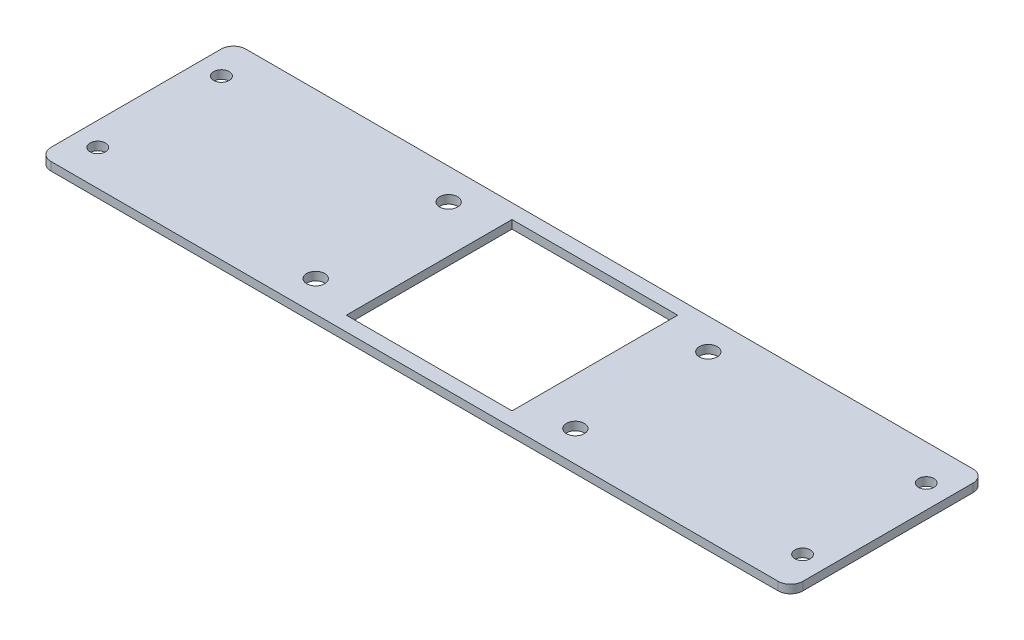
SolidWorks part; units mm, degrees
material "Acrylic (Medium-high impact)"
ref_plane "Front Plane" through (0, 0, 0) normal (0, 0, 1) x (1, 0, 0)
ref_plane "Top Plane" through (0, 0, 0) normal (0, 1, 0) x (1, 0, 0)
ref_plane "Right Plane" through (0, 0, 0) normal (1, 0, 0) x (0, 0, -1)
sketch "Sketch1" plane through (0, 0, 0) normal (0, 1, 0) x (1, 0, 0)
  line L0 (-60.8, -12.3481) -> (-60.8, -7.25) construction
  line L1 (-59.8, -6.25) -> (-53, -6.25) construction
  line L2 (-52, -7.25) -> (-52, -13.349) construction
  line L3 (-53, -14.35) -> (-58.8, -14.35) construction
  line L4 (-53, 6.25) -> (-59.8, 6.25) construction
  line L5 (-60.8, 7.25) -> (-60.8, 12.3481) construction
  line L6 (-58.8, 14.35) -> (-53, 14.35) construction
  line L7 (-52, 13.349) -> (-52, 7.25) construction
  line L8 (53, -6.25) -> (59.8, -6.25) construction
  line L9 (60.8, -7.25) -> (60.8, -12.3481) construction
  line L10 (58.8, -14.35) -> (53, -14.35) construction
  line L11 (52, -13.349) -> (52, -7.25) construction
  line L12 (60.8, 12.3481) -> (60.8, 7.25) construction
  line L13 (59.8, 6.25) -> (53, 6.25) construction
  line L14 (52, 7.25) -> (52, 13.349) construction
  line L15 (53, 14.35) -> (58.8, 14.35) construction
  line L16 (-60.8, -12.3481) -> (-60.8, -7.25)
  line L17 (-59.8, -6.25) -> (-53, -6.25)
  line L18 (-52, -7.25) -> (-52, -13.349)
  line L19 (-53, -14.35) -> (-58.8, -14.35)
  line L20 (-53, 6.25) -> (-59.8, 6.25)
  line L21 (-60.8, 7.25) -> (-60.8, 12.3481)
  line L22 (-58.8, 14.35) -> (-53, 14.35)
  line L23 (-52, 13.349) -> (-52, 7.25)
  line L24 (53, -6.25) -> (59.8, -6.25)
  line L25 (60.8, -7.25) -> (60.8, -12.3481)
  line L26 (58.8, -14.35) -> (53, -14.35)
  line L27 (52, -13.349) -> (52, -7.25)
  line L28 (60.8, 12.3481) -> (60.8, 7.25)
  line L29 (59.8, 6.25) -> (53, 6.25)
  line L30 (52, 7.25) -> (52, 13.349)
  line L31 (53, 14.35) -> (58.8, 14.35)
  line L32 (-60.8, 15.75) -> (60.8, 15.75)
  line L33 (104.5, 15.75) -> (-104.5, 15.75) construction
  line L34 (-60.8, -15.75) -> (60.8, -15.75)
  line L35 (-66.88, -15.75) -> (66.88, -15.75) construction
  arc A0 (-59.8, -6.25) -> (-60.8, -7.25) centre (-59.8, -7.25) ccw construction
  circle A1 centre (-57, 10) radius 1.6
  circle A2 centre (-57, 10) radius 1.6
  circle A3 centre (-57, -10) radius 1.6
  circle A4 centre (-57, -10) radius 1.6
  circle A5 centre (57, -10) radius 1.6
  circle A6 centre (57, -10) radius 1.6
  circle A7 centre (57, 10) radius 1.6
  circle A8 centre (57, 10) radius 1.6
  arc A9 (-52, -7.25) -> (-53, -6.25) centre (-53, -7.25) ccw construction
  arc A10 (-60.8, 7.25) -> (-59.8, 6.25) centre (-59.8, 7.25) ccw construction
  arc A11 (-53, 6.25) -> (-52, 7.25) centre (-53, 7.25) ccw construction
  arc A12 (60.8, -7.25) -> (59.8, -6.25) centre (59.8, -7.25) ccw construction
  arc A13 (53, -6.25) -> (52, -7.25) centre (53, -7.25) ccw construction
  arc A14 (59.8, 6.25) -> (60.8, 7.25) centre (59.8, 7.25) ccw construction
  arc A15 (52, 7.25) -> (53, 6.25) centre (53, 7.25) ccw construction
  arc A16 (-59.8, -6.25) -> (-60.8, -7.25) centre (-59.8, -7.25) ccw
  arc A17 (-52, -7.25) -> (-53, -6.25) centre (-53, -7.25) ccw
  arc A18 (-60.8, 7.25) -> (-59.8, 6.25) centre (-59.8, 7.25) ccw
  arc A19 (-53, 6.25) -> (-52, 7.25) centre (-53, 7.25) ccw
  arc A20 (60.8, -7.25) -> (59.8, -6.25) centre (59.8, -7.25) ccw
  arc A21 (53, -6.25) -> (52, -7.25) centre (53, -7.25) ccw
  arc A22 (59.8, 6.25) -> (60.8, 7.25) centre (59.8, 7.25) ccw
  arc A23 (52, 7.25) -> (53, 6.25) centre (53, 7.25) ccw
  ellipse E0 centre (-53, -13.349) end of major axis (-53, -14.35) minor radius 1 (-53, -14.35) -> (-52, -13.349) ccw construction
  ellipse E1 centre (-58.8, -12.3481) end of major axis (-58.8, -10.3461) minor radius 2 (-60.8, -12.3481) -> (-58.8, -14.35) ccw construction
  ellipse E2 centre (-58.8, 12.3481) end of major axis (-58.8, 14.35) minor radius 2 (-58.8, 14.35) -> (-60.8, 12.3481) ccw construction
  ellipse E3 centre (-53, 13.349) end of major axis (-53, 14.35) minor radius 1 (-52, 13.349) -> (-53, 14.35) ccw construction
  ellipse E4 centre (58.8, -12.3481) end of major axis (58.8, -14.35) minor radius 2 (58.8, -14.35) -> (60.8, -12.3481) ccw construction
  ellipse E5 centre (53, -13.349) end of major axis (53, -14.35) minor radius 1 (52, -13.349) -> (53, -14.35) ccw construction
  ellipse E6 centre (53, 13.349) end of major axis (53, 14.35) minor radius 1 (53, 14.35) -> (52, 13.349) ccw construction
  ellipse E7 centre (58.8, 12.3481) end of major axis (58.8, 10.3461) minor radius 2 (60.8, 12.3481) -> (58.8, 14.35) ccw construction
  ellipse E8 centre (-53, -13.349) end of major axis (-53, -14.35) minor radius 1 (-53, -14.35) -> (-52, -13.349) ccw
  ellipse E9 centre (-58.8, -12.3481) end of major axis (-58.8, -10.3461) minor radius 2 (-60.8, -12.3481) -> (-58.8, -14.35) ccw
  ellipse E10 centre (-58.8, 12.3481) end of major axis (-58.8, 14.35) minor radius 2 (-58.8, 14.35) -> (-60.8, 12.3481) ccw
  ellipse E11 centre (-53, 13.349) end of major axis (-53, 14.35) minor radius 1 (-52, 13.349) -> (-53, 14.35) ccw
  ellipse E12 centre (58.8, -12.3481) end of major axis (58.8, -14.35) minor radius 2 (58.8, -14.35) -> (60.8, -12.3481) ccw
  ellipse E13 centre (53, -13.349) end of major axis (53, -14.35) minor radius 1 (52, -13.349) -> (53, -14.35) ccw
  ellipse E14 centre (53, 13.349) end of major axis (53, 14.35) minor radius 1 (53, 14.35) -> (52, 13.349) ccw
  ellipse E15 centre (58.8, 12.3481) end of major axis (58.8, 10.3461) minor radius 2 (60.8, 12.3481) -> (58.8, 14.35) ccw
  dimension "D1" = 0
  dimension "D2" = 0
  dimension "D3" = 0
  dimension "D4" = 0
sketch "Sketch2" plane through (0, 0, 0) normal (0, 1, 0) x (1, 0, 0)
  line L1 (-60.8, -15.75) -> (60.8, -15.75)
  line L2 (-60.8, -15.75) -> (-60.8, 15.75)
  line L3 (-60.8, 15.75) -> (60.8, 15.75)
  line L4 (60.8, -15.75) -> (60.8, 15.75)
  circle A0 centre (-57, 10) radius 1.25
  circle A1 centre (-57, -10) radius 1.25
  circle A2 centre (57, 10) radius 1.25
  circle A3 centre (57, -10) radius 1.25
  dimension "D1" = 2.5
extrude "Boss-Extrude1" add sketch "Sketch2" against normal blind 1.35
fillet "Fillet1" radius 2 4 edges at (-60.8, -0.675, -15.75) (60.8, -0.675, -15.75) (60.8, -0.675, 15.75) (-60.8, -0.675, 15.75)
sketch "Sketch3" plane through (0, 0, 0) normal (0, 1, 0) x (1, 0, 0)
  line L4 (13.4, -13.4) -> (13.4, 13.4)
  line L5 (13.4, 13.4) -> (-13.4, 13.4)
  line L6 (-13.4, 13.4) -> (-13.4, -13.4)
  line L7 (-13.4, -13.4) -> (13.4, -13.4)
  line L8 (13.4, -13.4) -> (13.4, 13.4)
  line L9 (13.4, 13.4) -> (-13.4, 13.4)
  line L10 (-13.4, 13.4) -> (-13.4, -13.4)
  line L11 (-13.4, -13.4) -> (13.4, -13.4)
  circle A1 centre (-21, -10.75) radius 1.75
  circle A2 centre (-21, -10.75) radius 1.75 construction
  circle A3 centre (21, -10.75) radius 1.75
  circle A4 centre (21, -10.75) radius 1.75 construction
  circle A5 centre (21, 10.75) radius 1.75
  circle A6 centre (21, 10.75) radius 1.75 construction
  circle A7 centre (-21, 10.75) radius 1.75
  circle A8 centre (-21, 10.75) radius 1.75 construction
  circle A12 centre (-21, 10.75) radius 1.45
  circle A13 centre (21, 10.75) radius 1.45
  circle A14 centre (21, -10.75) radius 1.45
  circle A15 centre (-21, -10.75) radius 1.45
  dimension "D5" = 2.9
  dimension "D1" = 0
  dimension "D2" = 0
  dimension "D3" = 0
  dimension "D4" = 0
  dimension "D6" = 0
extrude "Cut-Extrude1" cut sketch "Sketch3" against normal through all
equation "\"Black_acrylic\"= 1.35mm"
